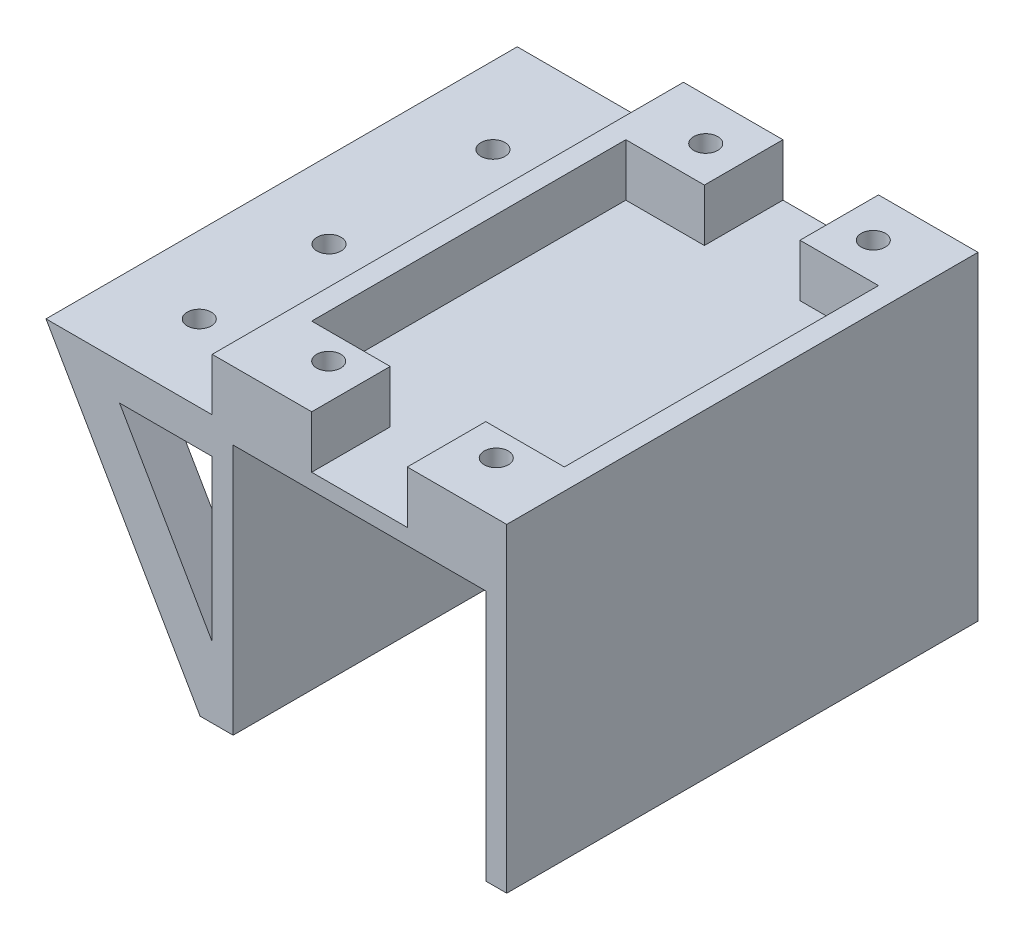
SolidWorks part; units mm, degrees
ref_plane "Front" through (0, 0, 0) normal (0, 0, 1) x (1, 0, 0)
ref_plane "Top" through (0, 0, 0) normal (0, 1, 0) x (1, 0, 0)
ref_plane "Right" through (0, 0, 0) normal (1, 0, 0) x (0, 0, -1)
sketch "Sketch1" plane through (0, 0, 0) normal (0, 0, 1) x (1, 0, 0)
  line L0 (0, 0) -> (0, 70)
  line L1 (0, 70) -> (56.254, 70)
  line L2 (56.254, 70) -> (56.254, 0)
  line L3 (56.254, 0) -> (52.254, 0)
  line L4 (52.254, 0) -> (52.254, 65)
  line L5 (52.254, 65) -> (4, 65)
  line L6 (4, 65) -> (4, 0)
  line L7 (4, 0) -> (0, 0)
  line L9 (4, 55) -> (52.254, 55)
  line L10 (4, 55) -> (4, 52)
  line L11 (4, 52) -> (52.254, 52)
  line L12 (52.254, 55) -> (52.254, 52)
  dimension "D1" = 48.254
  dimension "D2" = 4
  dimension "D3" = 4
  dimension "D4" = 5
  dimension "D5" = 70
  dimension "D6" = 3
  dimension "D7" = 10
extrude "Boss-Extrude1" add sketch "Sketch1" along normal blind 70 contours L7 L6 L5 L4 L3 L2 L1 L0 | L9 L12 L11 L10 region at (0.898, 35, 0)
sketch "Sketch3" plane through (0, 0, 70) normal (0, 0, 1) x (1, 0, 0)
  line L0 (0, 70) -> (-40.3946, 70)
  line L1 (-40.3946, 70) -> (0, 0.0344)
  line L2 (0, 0) -> (0, 70) construction
  line L3 (0, 0.0344) -> (0, 70)
  line L4 (0, 70) -> (0, 62.5)
  line L5 (0, 62.5) -> (-26, 62.5)
  line L6 (-26, 62.5) -> (0, 17.4667)
  line L7 (0, 17.4667) -> (0, 0.0344)
  line M11 (0, 70) -> (0, 0)
  dimension "D1" = 60
  dimension "D2" = 180
  dimension "D3" = 7.5
  dimension "D4" = 26
extrude "Boss-Extrude3" add sketch "Sketch3" against normal blind 8 contours L6 L5 L0 L1 M11 region at (-16.8587, 46.1047, 70)
sketch "Sketch4" plane through (0, 0, 0) normal (0, 0, -1) x (-1, 0, 0)
  line L0 (0, 70) -> (40.3946, 70)
  line L1 (40.3946, 70) -> (0, 0)
  line L2 (0, 0) -> (0, 17.4667)
  line L3 (0, 17.4667) -> (26, 62.5)
  line L4 (26, 62.5) -> (0, 62.5)
  line L5 (0, 62.5) -> (0, 70)
extrude "Boss-Extrude4" add sketch "Sketch4" against normal blind 8
ref_plane "Plane1" through (0, 0, 39) normal (0, 0, -1) x (-1, 0, 0)
sketch "Sketch5" plane through (0, 0, 39) normal (0, 0, -1) x (-1, 0, 0)
  line L0 (0, 62.5) -> (0, 70)
  line L1 (0, 70) -> (40.3946, 70)
  line L2 (40.3946, 70) -> (0, 0)
  line L3 (0, 0) -> (0, 17.4667)
  line L4 (0, 17.4667) -> (26, 62.5)
  line L5 (26, 62.5) -> (0, 62.5)
extrude "Boss-Extrude5" add sketch "Sketch5" along normal blind 8
sketch "Sketch6" plane through (0, 0, 0) normal (0, 0, -1) x (-1, 0, 0)
  line L5 (0, 62.5) -> (36.0666, 62.5)
  line L6 (0, 0) -> (40.3946, 70) construction
  line L7 (36.0666, 62.5) -> (40.3946, 70)
  line L8 (40.3946, 70) -> (0, 70)
  line L9 (40.3946, 70) -> (-56.254, 70) construction
  line L10 (0, 70) -> (0, 62.5)
  line L11 (-4, 0) -> (0, 0)
  line L12 (0, 0) -> (7.5019, 13)
  line L13 (7.5019, 13) -> (-4, 13)
  line L14 (-4, 52) -> (-4, 0) construction
  line L15 (-4, 13) -> (-4, 0)
  dimension "D1" = 13
extrude "Boss-Extrude6" add sketch "Sketch6" against normal blind 70
sketch "Sketch7" plane through (0, 0, 70) normal (0, 0, 1) x (1, 0, 0)
  line L0 (0, 17.4667) -> (0, 62.5) construction
  line L1 (-40.3946, 70) -> (0, 70)
  line L2 (-40.3946, 70) -> (-40.3946, 53)
  line L3 (-40.3946, 53) -> (0, 53)
  line L4 (0, 70) -> (0, 53)
  dimension "D1" = 17
extrude "Cut-Extrude3" cut sketch "Sketch7" against normal blind 70
sketch "Sketch8" plane through (0, 0, 0) normal (0, 0, -1) x (-1, 0, 0)
  line L1 (-4, 55) -> (-4, 52)
  line L2 (-4, 52) -> (-52.254, 52) construction
  line L3 (-4, 52) -> (30.0074, 52)
  line L4 (0, 0) -> (30.5845, 53) construction
  line L6 (30.0074, 52) -> (31.7386, 55)
  line L7 (31.7386, 55) -> (-4, 55)
  dimension "D1" = 180
extrude "Boss-Extrude7" add sketch "Sketch8" against normal blind 70
sketch "Sketch11" plane through (0, 0, 70) normal (0, 0, 1) x (1, 0, 0)
  line L0 (-31.7386, 55) -> (0, 0)
  line L3 (-31.7386, 55) -> (0, 55) construction
  line L4 (-27.289, 55) -> (-31.7386, 55)
  line L5 (-27.289, 55) -> (-3.0537, 13)
  line L6 (-3.0537, 13) -> (0, 0)
extrude "Boss-Extrude10" add sketch "Sketch11" against normal blind 8
sketch "Sketch12" plane through (0, 0, 70) normal (0, 0, 1) x (1, 0, 0)
  line L0 (-31.7386, 55) -> (-27.7598, 48.1051)
  line L1 (0, 0) -> (-31.7386, 55) construction
  line L2 (-27.7598, 48.1051) -> (0, 48.1051)
  line L3 (0, 17.4667) -> (0, 52) construction
  line L4 (0, 48.1051) -> (0, 55)
  line L5 (0, 55) -> (-31.7386, 55)
extrude "Boss-Extrude11" add sketch "Sketch12" against normal blind 70
sketch "Sketch13" plane through (0, 0, 0) normal (0, -1, 0) x (1, 0, 0)
  line L1 (67.4394, -10.6205) -> (-15.562, -10.6205)
  line L2 (67.4394, -10.6205) -> (67.4394, 77.2481)
  line L3 (67.4394, 77.2481) -> (-15.562, 77.2481)
  line L4 (-15.562, -10.6205) -> (-15.562, 77.2481)
extrude "Cut-Extrude4" cut sketch "Sketch13" against normal blind 4
sketch "Sketch14" plane through (0, 0, 70) normal (0, 0, 1) x (1, 0, 0)
  line L0 (-2.3083, 4) -> (-31.7386, 55)
  line L1 (-31.7386, 55) -> (0, 55)
  line L2 (0, 55) -> (0, 70)
  line L3 (0, 70) -> (56.254, 70)
  line L4 (56.254, 70) -> (56.254, 4)
  line L5 (56.254, 4) -> (52.254, 4)
  line L6 (52.254, 4) -> (52.254, 52)
  line L7 (52.254, 52) -> (4, 52)
  line L8 (4, 52) -> (4, 4)
  line L9 (4, 4) -> (-2.3083, 4)
  line L14 (-17.6891, 48.1051) -> (0, 48.1051)
  line L15 (52.254, 55) -> (4, 55)
  line L16 (52.254, 55) -> (52.254, 65)
  line L17 (52.254, 65) -> (4, 65)
  line L18 (4, 55) -> (4, 65)
  line L19 (-17.6891, 48.1051) -> (0, 48.1051) construction
  line L20 (0, 48.1051) -> (0, 17.4667)
  line L21 (0, 17.4667) -> (-17.6891, 48.1051)
extrude "Boss-Extrude12" add sketch "Sketch14" along normal blind 20
sketch "Sketch15" plane through (0, 0, 90) normal (0, 0, 1) x (1, 0, 0)
  line L0 (56.254, 4) -> (56.254, 70) construction
  line L1 (56.254, 65) -> (37.264, 65)
  line L2 (56.254, 65) -> (56.254, 55)
  line L3 (56.254, 55) -> (37.264, 55)
  line L4 (37.264, 65) -> (37.264, 55)
  line L5 (4, 55) -> (52.254, 55) construction
  dimension "D1" = 18.99
sketch "Sketch16" plane through (0, 0, 90) normal (0, 0, 1) x (1, 0, 0)
  line L1 (0, 70) -> (56.254, 70)
  line L2 (0, 70) -> (0, 65)
  line L3 (0, 65) -> (56.254, 65)
  line L4 (56.254, 70) -> (56.254, 65)
extrude "Cut-Extrude5" cut sketch "Sketch16" against normal blind 100
sketch "Sketch17" plane through (0, 65, 0) normal (0, 1, 0) x (1, 0, 0)
  line L1 (52.254, 0) -> (37.254, 0)
  line L2 (52.254, 0) -> (52.254, -15)
  line L3 (52.254, -15) -> (37.254, -15)
  line L4 (37.254, 0) -> (37.254, -15)
  line L5 (52.254, -90) -> (37.254, -90)
  line L6 (52.254, -90) -> (52.254, -75)
  line L7 (52.254, -75) -> (37.254, -75)
  line L8 (37.254, -90) -> (37.254, -75)
  dimension "D1" = 15
  dimension "D2" = 15
  dimension "D3" = 15
  dimension "D4" = 15
extrude "Boss-Extrude14" add sketch "Sketch17" against normal blind 13
sketch "Sketch21" plane through (0, 52, 0) normal (0, -1, 0) x (-1, 0, 0)
  circle A0 centre (-44.254, -80) radius 2.3
  circle A1 centre (-44.254, -8) radius 2.3
sketch "Sketch22" plane through (0, 52, 0) normal (0, -1, 0) x (1, 0, 0)
  line L1 (48.0965, 6.0036) -> (47.9041, 10.3295)
  line L2 (47.9041, 10.3295) -> (44.0617, 12.3259)
  line L3 (44.0617, 12.3259) -> (40.4115, 9.9964)
  line L4 (40.4115, 9.9964) -> (40.6039, 5.6705)
  line L5 (40.6039, 5.6705) -> (44.4463, 3.6741)
  line L6 (44.4463, 3.6741) -> (48.0965, 6.0036)
  line L7 (45.2007, 75.7746) -> (48.3866, 78.7072)
  line L8 (48.3866, 78.7072) -> (47.4399, 82.9325)
  line L9 (47.4399, 82.9325) -> (43.3073, 84.2254)
  line L10 (43.3073, 84.2254) -> (40.1214, 81.2928)
  line L11 (40.1214, 81.2928) -> (41.0681, 77.0675)
  line L12 (41.0681, 77.0675) -> (45.2007, 75.7746)
  circle A0 centre (44.254, 8) radius 3.75 construction
  circle A1 centre (44.254, 80) radius 3.75 construction
  point P10 (42.2366, 11.1611)
  dimension "D1" = 7.5
  dimension "D2" = 7.5
extrude "Cut-Extrude8" cut sketch "Sketch22" against normal blind 5
extrude "Cut-Extrude9" cut sketch "Sketch21" against normal blind 15
sketch "Sketch23" plane through (0, 0, 0) normal (-0.8661, -0.4998, 0) x (0, 0, 1)
  line L0 (90, 63.5007) -> (90, 4.6182) construction
  line L1 (70, 55.5401) -> (82, 55.5401)
  line L2 (70, 55.5401) -> (70, 15.0093)
  line L3 (70, 15.0093) -> (82, 15.0093)
  line L4 (82, 55.5401) -> (82, 15.0093)
  line L5 (62, 55.5401) -> (62, 15.0093) construction
  dimension "D1" = 8
  dimension "D2" = 8
extrude "Cut-Extrude10" cut sketch "Sketch23" against normal blind 9
sketch "Sketch25" plane through (0, 48.1051, 0) normal (0, -1, 0) x (-1, 0, 0)
  circle A0 centre (17.0755, -19.3006) radius 2.3
  circle A1 centre (17.0755, -50.6137) radius 2.3
extrude "Cut-Extrude11" cut sketch "Sketch25" against normal blind 20
sketch "Sketch26" plane through (0, 48.1051, 0) normal (0, -1, 0) x (1, 0, 0)
  circle A0 centre (-17.0755, 75.3913) radius 2.3
extrude "Cut-Extrude12" cut sketch "Sketch26" against normal blind 20
sketch "Sketch27" plane through (0, 0, 90) normal (0, 0, 1) x (1, 0, 0)
  line L0 (-23.3104, 48.1051) -> (-27.7598, 48.1051)
  line L1 (-31.7386, 55) -> (-2.3083, 4) construction
  line L2 (-27.7598, 48.1051) -> (-31.7386, 55)
  line L3 (-31.7386, 55) -> (-23.3104, 55)
  line L4 (0, 55) -> (-31.7386, 55) construction
  line L5 (-23.3104, 55) -> (-23.3104, 48.1051)
extrude "Boss-Extrude16" add sketch "Sketch27" against normal blind 20
sketch "Sketch28" plane through (0, 55, 0) normal (0, 1, 0) x (1, 0, 0)
  line L0 (4, -90) -> (37.254, -90) construction
  line L1 (4, 0) -> (19, 0)
  line L2 (4, 0) -> (4, -15)
  line L3 (4, -15) -> (19, -15)
  line L4 (19, 0) -> (19, -15)
  line L5 (4, -90) -> (19, -90)
  line L6 (4, -90) -> (4, -75)
  line L7 (4, -75) -> (19, -75)
  line L8 (19, -90) -> (19, -75)
  line L9 (4, 0) -> (4, -90) construction
  dimension "D1" = 15
  dimension "D2" = 15
  dimension "D3" = 15
  dimension "D4" = 15
extrude "Boss-Extrude17" add sketch "Sketch28" along normal blind 10
sketch "Sketch29" plane through (0, 52, 0) normal (0, -1, 0) x (-1, 0, 0)
  circle A0 centre (-12.254, -8) radius 2.3
  circle A1 centre (-12.254, -80) radius 2.3
extrude "Cut-Extrude13" cut sketch "Sketch29" against normal blind 20
sketch "Sketch30" plane through (0, 48.1051, 0) normal (0, -1, 0) x (1, 0, 0)
  line L1 (-27.7598, 70) -> (-17.3688, 70)
  line L2 (-27.7598, 70) -> (-27.7598, 82)
  line L3 (-27.7598, 82) -> (-17.3688, 82)
  line L4 (-17.3688, 70) -> (-17.3688, 82)
extrude "Boss-Extrude18" add sketch "Sketch30" against normal blind 5
sketch "Sketch31" plane through (0, 48.1051, 0) normal (0, -1, 0) x (1, 0, 0)
  circle A0 centre (-17.0755, 75.3913) radius 2.3
extrude "Cut-Extrude14" cut sketch "Sketch31" against normal blind 45
sketch "Sketch33" plane through (0, 55, 0) normal (0, 1, 0) x (1, 0, 0)
  circle A0 centre (27.6164, -46.5233) radius 1
  circle A1 centre (26.8974, -20.9206) radius 1
  circle A2 centre (28.9102, -66.6327) radius 1
  circle A3 centre (-20.9687, -5.2719) radius 1
  circle A4 centre (-23.4497, -23.5026) radius 1
  circle A5 centre (-17.8546, -42.0102) radius 1
  circle A6 centre (-22.4497, -64.7625) radius 1
  circle A7 centre (-17.8546, -85.6157) radius 1
